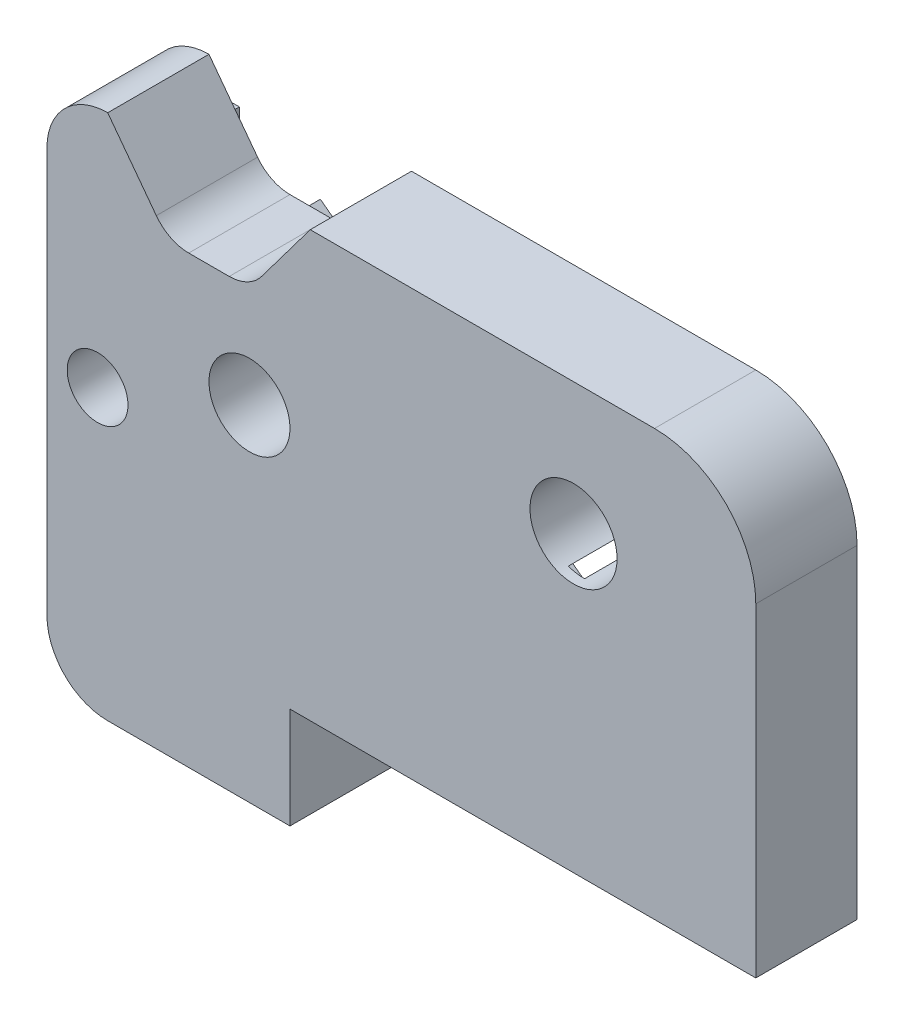
SolidWorks part; units mm, degrees
ref_plane "Front" through (0, 0, 0) normal (0, 0, 1) x (1, 0, 0)
ref_plane "Top" through (0, 0, 0) normal (0, 1, 0) x (1, 0, 0)
ref_plane "Right" through (0, 0, 0) normal (1, 0, 0) x (0, 0, -1)
sketch "Sketch1" plane through (0, 0, 0) normal (0, 0, 1) x (1, 0, 0)
  line L0 (-8, 6.5) -> (-8, -14.5)
  line L1 (-8, -14.5) -> (15, -14.5)
  line L2 (15, -14.5) -> (15, 6.5)
  line L3 (15, 6.5) -> (-8, 6.5)
  dimension "D1" = 8
  dimension "D2" = 15
  dimension "D3" = 6.5
  dimension "D4" = 14.5
extrude "Extrude1" add sketch "Sketch1" along normal blind 5
sketch "Sketch2" plane through (0, 0, 5) normal (0, 0, 1) x (1, 0, 0)
  circle A0 centre (6, 0) radius 2.15
  dimension "D1" = 4.3
  dimension "D2" = 6
extrude "Extrude2" cut sketch "Sketch2" against normal blind 4.5
sketch "Sketch4" plane through (0, -14.5, 0) normal (0, -1, 0) x (1, 0, 0)
  line L0 (-8, 0) -> (15, 0) construction
  line L1 (-8, 5) -> (-8, 0) construction
  line L2 (15, 5) -> (15, 0) construction
  circle A0 centre (-1.4, 2.5) radius 1.25
  circle A1 centre (12, 2.5) radius 1.25
  dimension "D1" = 2.5
  dimension "D2" = 2.5
  dimension "D3" = 2.5
  dimension "D5" = 6.6
  dimension "D6" = 3
  dimension "D4" = 2.5
extrude "Extrude4" cut sketch "Sketch4" against normal blind 8
cosmetic thread "Hole Thread1" parameters "D1"=6, "D2"=3
cosmetic thread "Hole Thread2" parameters "D1"=6, "D2"=3
fillet "Fillet1" radius 5 1 edges at (15, 6.5, 2.5)
sketch "Sketch6" plane through (0, 0, 0) normal (0, 0, -1) x (-1, 0, 0)
  line L0 (8, -14.5) -> (-15, -14.5) construction
  line L1 (8, 6.5) -> (8, -14.5) construction
  circle A0 centre (-4.9, -6.5) radius 4.5
  dimension "D1" = 9
  dimension "D3" = 12.9
  dimension "D2" = 8
extrude "Extrude6" cut sketch "Sketch6" against normal blind 4.5
sketch "Sketch9" plane through (0, 0, 0) normal (0, 0, -1) x (-1, 0, 0)
  line L1 (8, 6.5) -> (20, 6.5)
  line L2 (8, 6.5) -> (8, -19.5)
  line L3 (8, -19.5) -> (20, -19.5)
  line L4 (20, 6.5) -> (20, -19.5)
  line L5 (8, -14.5) -> (-15, -14.5) construction
  dimension "D1" = 12
  dimension "D2" = 5
extrude "Extrude9" add sketch "Sketch9" against normal up to surface (5 mm away) up to face at (8.15, 0, 5)
sketch "Sketch11" plane through (0, 0, 5) normal (0, 0, 1) x (1, 0, 0)
  line L0 (-20, -19.5) -> (-20, 6.5) construction
  line L1 (-8, -14.5) -> (15, -14.5) construction
  circle A0 centre (-17.5, -5.5) radius 1.5
  dimension "D1" = 3
  dimension "D3" = 9
  dimension "D2" = 2.5
extrude "Extrude11" cut sketch "Sketch11" against normal up to surface (5 mm away) up to face at (0.4, -6.5, 0)
sketch "Sketch10" plane through (0, 0, 5) normal (0, 0, 1) x (1, 0, 0)
  line L0 (10, 6.5) -> (-20, 6.5) construction
  line L1 (-20, -19.5) -> (-20, 6.5) construction
  circle A0 centre (-10, -2.5) radius 2
  dimension "D1" = 4
  dimension "D3" = 10
  dimension "D2" = 9
extrude "Extrude10" cut sketch "Sketch10" against normal blind 4
hole_wizard "M3 Tapped Hole1" positions "3DSketch1" profile "Sketch12" tap size "M3" standard "DIN"
sketch3d "3DSketch1"
  line L0 (-1.4, -6.5, 2.5) -> (-1.4, -14.5, 2.5) construction
  line L1 (12, -6.5, 2.5) -> (12, -14.5, 2.5) construction
  point P0 (-1.4, -14.5, 2.5)
  point P4 (12, -14.5, 2.5)
sketch "Sketch12" plane through (-1.4, -14.5, 2.5) normal (1, 0, 0) x (0, 0, -1)
  line L0 (0, 0) -> (0, 8.7511)
  line L1 (0, 8.7511) -> (1.25, 8)
  line L2 (1.25, 8) -> (1.25, 0)
  line L5 (1.25, 0) -> (0, 0)
  line L10 (0, 8.7511) -> (-1.25, 8) construction
  line L11 (0, -6.35) -> (0, 107.95) construction
  dimension "Tap Drill Dia." = 2.5
  dimension "Tap Drill Depth" = 8
  dimension "Drill Angle" = 118
sketch "Sketch13" plane through (0, 0, 0) normal (0, 0, -1) x (-1, 0, 0)
  line L0 (20, -19.5) -> (8, -19.5)
  line L1 (20, -19.5) -> (20, 1)
  line L2 (20, 1) -> (18.1, 1)
  line L3 (20, -19.5) -> (20, 6.5) construction
  line L4 (18.1, 1) -> (2, -11.07)
  line L5 (2, -11.07) -> (2, -14.5)
  line L6 (8, -14.5) -> (-15, -14.5) construction
  line L7 (2, -14.5) -> (8, -14.5)
  line L8 (8, -14.5) -> (8, -19.5)
  dimension "D1" = 18
  dimension "D2" = 20.5
  dimension "D3" = 1.9
  dimension "D4" = 8.43
extrude "Extrude12" add sketch "Sketch13" along normal blind 4
fillet "Fillet3" radius 3 2 edges at (-20, -19.5, 0.5) (-20, 6.5, 2.5)
sketch "Sketch14" plane through (0, 0, -4) normal (0, 0, -1) x (-1, 0, 0)
  line L0 (19.5, 1) -> (19.5, -7.5)
  line L1 (20, 1) -> (18.1, 1) construction
  line L2 (19.5, -7.5) -> (15.5, -7.5)
  line L3 (15.5, -7.5) -> (15.5, -0.9492)
  line L4 (18.1, 1) -> (2, -11.07) construction
  line L5 (15.5, -0.9492) -> (18.1, 1)
  line L6 (18.1, 1) -> (19.5, 1)
  line L8 (20, -16.5) -> (20, 1) construction
  dimension "D1" = 4
  dimension "D2" = 8.5
  dimension "D3" = 0.5
extrude "Extrude14" cut sketch "Sketch14" against normal up to surface (4 mm away) up to face at (0.4, -6.5, 0)
fillet "Fillet4" radius 2 2 edges at (-19.5, -7.5, -2) (-15.5, -7.5, -2)
sketch "Sketch15" plane through (0, 0, 5) normal (0, 0, 1) x (1, 0, 0)
  line L0 (-14, 2.5) -> (-17, 6.5)
  line L1 (10, 6.5) -> (-17, 6.5) construction
  line L2 (-14, 2.5) -> (-10, 2.5)
  line L3 (-10, 2.5) -> (-7, 6.5)
  line L4 (-17, 6.5) -> (-7, 6.5)
  line L5 (-20, -16.5) -> (-20, 3.5) construction
  dimension "D1" = 6
  dimension "D2" = 4
  dimension "D3" = 10
  dimension "D4" = 4
extrude "Extrude15" cut sketch "Sketch15" against normal up to surface (5 mm away) up to face at (-8.9874, -2.9404, 0)
fillet "Fillet6" radius 2 2 edges at (-10, 2.5, 2.5) (-14, 2.5, 2.5)
